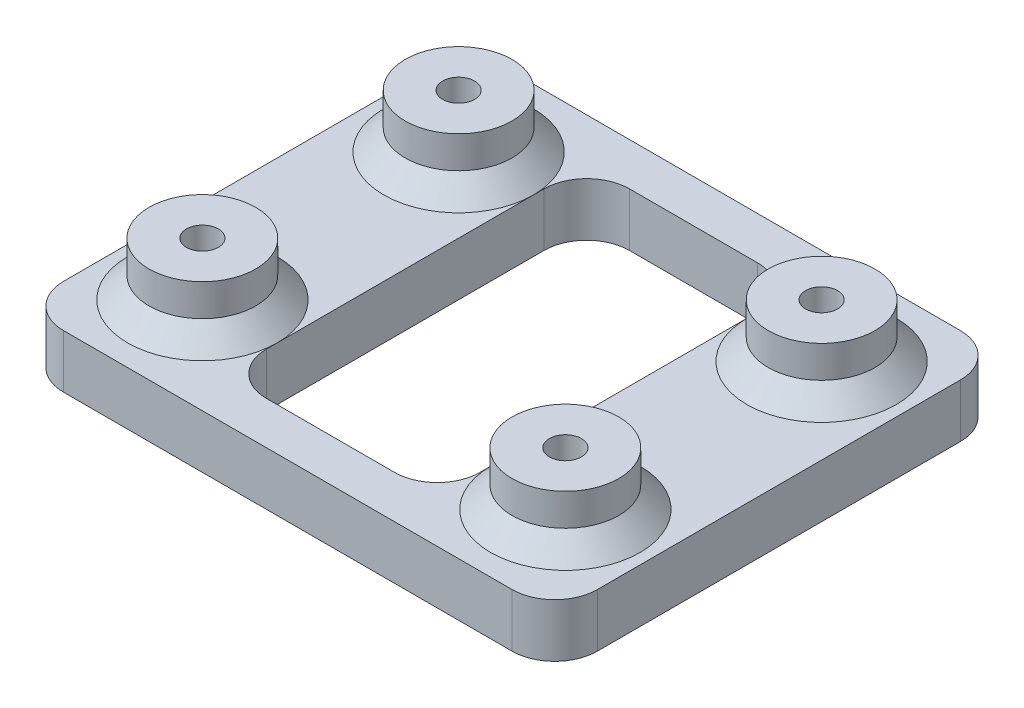
SolidWorks part; units mm, degrees
ref_plane "Front Plane" through (0, 0, 0) normal (0, 0, 1) x (1, 0, 0)
ref_plane "Top Plane" through (0, 0, 0) normal (0, 1, 0) x (1, 0, 0)
ref_plane "Right Plane" through (0, 0, 0) normal (1, 0, 0) x (0, 0, -1)
sketch "Sketch1" plane through (0, 0, 0) normal (0, 1, 0) x (1, 0, 0)
  line L1 (-15.875, -13.335) -> (15.875, -13.335)
  line L2 (-15.875, -13.335) -> (-15.875, 13.335)
  line L3 (-15.875, 13.335) -> (15.875, 13.335)
  line L4 (15.875, -13.335) -> (15.875, 13.335)
  line L5 (-15.875, -13.335) -> (15.875, 13.335) construction
  line L6 (-15.875, 13.335) -> (15.875, -13.335) construction
  point P0 (0, 0)
  dimension "D1" = 31.75
  dimension "D2" = 26.67
extrude "Boss-Extrude1" add sketch "Sketch1" along normal blind 3.175
sketch "Sketch2" plane through (0, 3.175, 0) normal (0, 1, 0) x (1, 0, 0)
  line L1 (-10.795, -7.62) -> (10.795, -7.62) construction
  line L2 (-10.795, -7.62) -> (-10.795, 7.62) construction
  line L3 (-10.795, 7.62) -> (10.795, 7.62) construction
  line L4 (10.795, -7.62) -> (10.795, 7.62) construction
  line L5 (-10.795, -7.62) -> (10.795, 7.62) construction
  line L6 (-10.795, 7.62) -> (10.795, -7.62) construction
  circle A0 centre (-10.795, 7.62) radius 0.95
  circle A1 centre (10.795, 7.62) radius 0.95
  circle A2 centre (10.795, -7.62) radius 0.95
  circle A3 centre (-10.795, -7.62) radius 0.95
  point P0 (0, 0)
  dimension "D3" = 1.9
  dimension "D1" = 15.24
  dimension "D2" = 21.59
extrude "Cut-Extrude1" cut sketch "Sketch2" against normal through all
sketch "Sketch3" plane through (0, 3.175, 0) normal (0, 1, 0) x (1, 0, 0)
  circle A0 centre (-10.795, 7.62) radius 3.175
  circle A1 centre (10.795, 7.62) radius 3.175
  circle A2 centre (10.795, -7.62) radius 3.175
  circle A3 centre (-10.795, -7.62) radius 3.175
  circle A4 centre (-10.795, 7.62) radius 0.95 construction
  circle A5 centre (10.795, 7.62) radius 0.95 construction
  circle A6 centre (10.795, -7.62) radius 0.95 construction
  circle A7 centre (-10.795, -7.62) radius 0.95 construction
  circle A8 centre (-10.795, 7.62) radius 0.95
  circle A9 centre (10.795, 7.62) radius 0.95
  circle A10 centre (10.795, -7.62) radius 0.95
  circle A11 centre (-10.795, -7.62) radius 0.95
  point P10 (10.795, 7.62)
  point P12 (-10.795, -7.62)
  point P13 (-10.795, -7.62)
  dimension "D1" = 6.35
extrude "Boss-Extrude2" add sketch "Sketch3" along normal blind 3.175
sketch "Sketch4" plane through (0, 3.175, 0) normal (0, 1, 0) x (1, 0, 0)
  line L1 (-6.35, -10.795) -> (6.35, -10.795)
  line L2 (-6.35, -10.795) -> (-6.35, 10.795)
  line L3 (-6.35, 10.795) -> (6.35, 10.795)
  line L4 (6.35, -10.795) -> (6.35, 10.795)
  line L5 (-6.35, -10.795) -> (6.35, 10.795) construction
  line L6 (-6.35, 10.795) -> (6.35, -10.795) construction
  point P0 (0, 0)
  dimension "D1" = 12.7
  dimension "D2" = 21.59
extrude "Cut-Extrude2" cut sketch "Sketch4" against normal through all
fillet "Fillet1" radius 2.54 8 edges at (15.875, 1.5875, -13.335) (15.875, 1.5875, 13.335) (-15.875, 1.5875, 13.335) (-15.875, 1.5875, -13.335) (-6.35, 1.5875, 10.795) (6.35, 1.5875, 10.795) (6.35, 1.5875, -10.795) (-6.35, 1.5875, -10.795)
chamfer "Chamfer1" distance 1.27 angle 45 4 edges at (-10.795, 3.175, -10.795) (10.795, 3.175, -10.795) (10.795, 3.175, 4.445) (-10.795, 3.175, 4.445)
